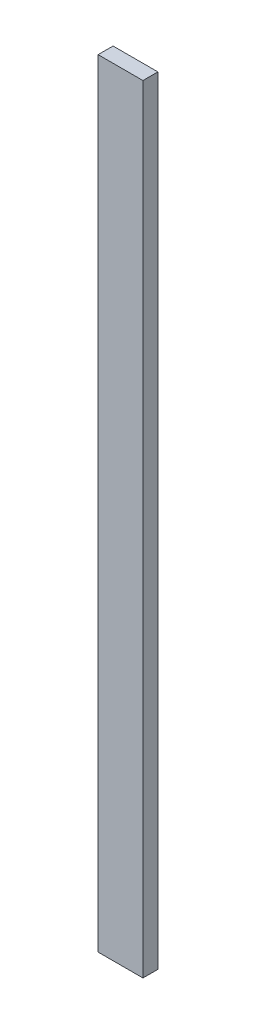
SolidWorks part; units mm, degrees
material "Plain Carbon Steel"
ref_plane "Front Plane" through (0, 0, 0) normal (0, 0, 1) x (1, 0, 0)
ref_plane "Top Plane" through (0, 0, 0) normal (0, 1, 0) x (1, 0, 0)
ref_plane "Right Plane" through (0, 0, 0) normal (1, 0, 0) x (0, 0, -1)
sketch "Sketch1" plane through (0, 0, 0) normal (0, 0, 1) x (1, 0, 0)
  line L1 (85, -11.4779) -> (55, -11.4779)
  line L2 (85, -11.4779) -> (85, -531.4779)
  line L3 (85, -531.4779) -> (55, -531.4779)
  line L4 (55, -11.4779) -> (55, -531.4779)
  line L5 (85, -11.4779) -> (55, -531.4779) construction
  line L6 (85, -531.4779) -> (55, -11.4779) construction
  line L7 (93, -531.4779) -> (47, -531.4779) construction
  point P0 (70, -271.4779)
  dimension "D1" = 30
extrude "Boss-Extrude1" add sketch "Sketch1" along normal blind 10
sketch "Center_lines" plane through (0, 0, 0) normal (0, 0, -1) x (-1, 0, 0)
  line L0 (-70, -11.4779) -> (-70, -531.4779) construction
  line L1 (-85, -11.4779) -> (-55, -11.4779) construction
  line L2 (-55, -531.4779) -> (-85, -531.4779) construction
  line L3 (-85, -271.4779) -> (-55, -271.4779) construction
  line L4 (-85, -531.4779) -> (-85, -11.4779) construction
  line L5 (-55, -11.4779) -> (-55, -531.4779) construction
sketch "Center_lines_top" plane through (0, 0, 10) normal (0, 0, 1) x (1, 0, 0)
  line L0 (70, -11.4779) -> (70, -531.4779) construction
  line L1 (55, -271.4779) -> (85, -271.4779) construction
  point P8 (70, -271.4779)
